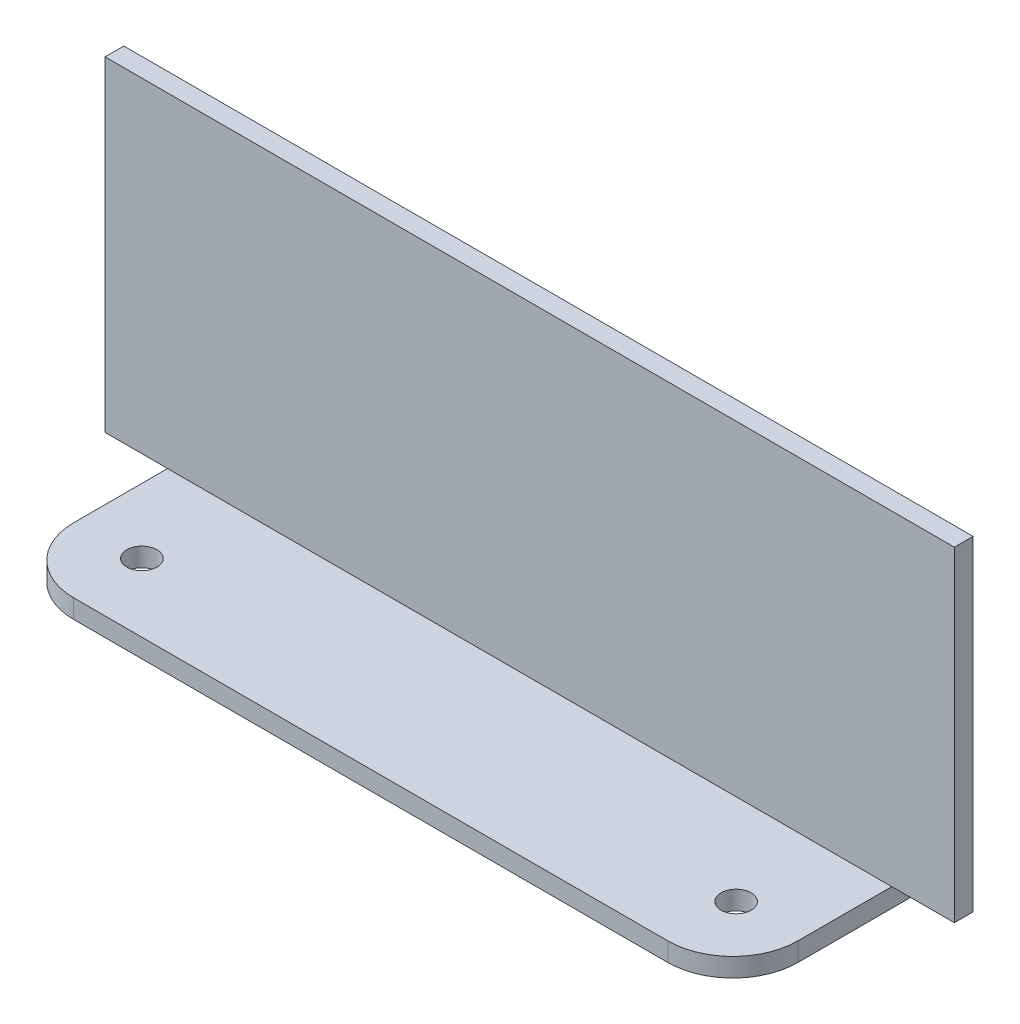
SolidWorks part; units mm, degrees
ref_plane "Front Plane" through (0, 0, 0) normal (0, 0, 1) x (1, 0, 0)
ref_plane "Top Plane" through (0, 0, 0) normal (0, 1, 0) x (1, 0, 0)
ref_plane "Right Plane" through (0, 0, 0) normal (1, 0, 0) x (0, 0, -1)
sketch "Sketch1" plane through (0, 0, 0) normal (0, 1, 0) x (1, 0, 0)
  line L0 (10.39, 0) -> (105.39, 0)
  line L3 (0, 11.43) -> (0, 10.39)
  line L4 (0, 10.91) -> (10.39, 10.91) construction
  line L5 (57.89, 21.82) -> (57.89, 0) construction
  line L6 (115.78, 11.43) -> (115.78, 10.39)
  line L7 (0, 10.91) -> (0, 25.41)
  line L8 (0, 25.41) -> (115.78, 25.41)
  line L9 (115.78, 11.43) -> (115.78, 10.91)
  line L10 (115.78, 10.91) -> (115.78, 25.41)
  line L12 (0, 25.41) -> (115.78, 25.41)
  line L13 (0, 25.41) -> (0, 28.41)
  line L14 (0, 28.41) -> (115.78, 28.41)
  line L15 (115.78, 25.41) -> (115.78, 28.41)
  arc A2 (10.39, 0) -> (0, 10.39) centre (10.39, 10.39) cw
  circle A4 centre (10.39, 10.91) radius 2.41
  arc A5 (105.39, 0) -> (115.78, 10.39) centre (105.39, 10.39) ccw
  circle A6 centre (105.39, 10.91) radius 2.41
  point P9 (115.78, 0)
  point P12 (0, 0)
  point P20 (57.89, 25.41)
  dimension "D2" = 10.39
  dimension "D5" = 4.82
  dimension "D1" = 115.78
  dimension "D3" = 57.89
  dimension "D4" = 10.39
  dimension "D6" = 3
  dimension "D7" = 14.5
  dimension "D8" = 10.91
extrude "Boss-Extrude1" add sketch "Sketch1" along normal blind 3 contours L0 A5 L6 L10 L8 L7 L3 A2 A4 A6 | L8 L15 L14 L13 region at (57.89, 0, -12.8962) region at (57.89, 0, -26.91)
extrude "Boss-Extrude2" add sketch "Sketch1<4>" along normal blind 55 contours L8 L15 L14 L13 region at (57.89, 0, -26.91)
sketch "Sketch1<4>" plane through (0, 0, 0) normal (0, 1, 0) x (1, 0, 0) same geometry as "Sketch1"
sketch "Sketch2" plane through (115.78, 0, 0) normal (1, 0, 0) x (0, 0, -1)
  line L0 (25.41, 55) -> (25.41, 3)
  line L1 (25.41, 3) -> (28.41, 3)
  line L2 (28.41, 55) -> (28.41, 0) construction
  line L3 (28.41, 3) -> (28.41, 55)
  line L4 (28.41, 55) -> (25.41, 55)
sketch "Sketch3" plane through (0, 0, 0) normal (-1, 0, 0) x (0, 0, 1)
  line L0 (-25.41, 3) -> (-28.41, 3)
  line L1 (-28.41, 3) -> (-28.41, 55)
  line L2 (-28.41, 55) -> (-25.41, 55)
  line L3 (-25.41, 55) -> (-25.41, 3)
extrude "Boss-Extrude3" add sketch "Sketch3" along normal blind 10
extrude "Boss-Extrude4" add sketch "Sketch2" along normal blind 10
